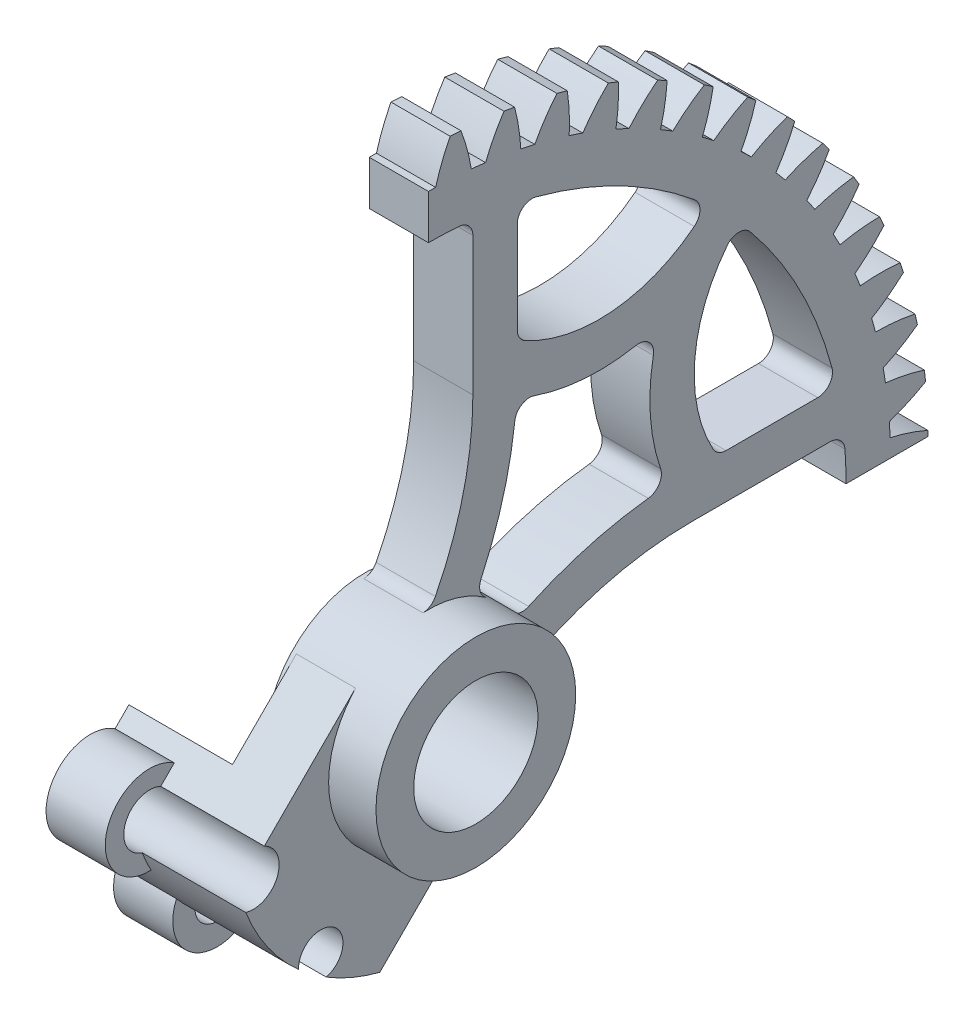
SolidWorks part; units mm, degrees
ref_plane "Plane1" through (0, 0, 0) normal (0, 0, 1) x (1, 0, 0)
ref_plane "Plane2" through (0, 0, 0) normal (0, 1, 0) x (1, 0, 0)
ref_plane "Plane3" through (0, 0, 0) normal (1, 0, 0) x (0, 0, -1)
sketch "HoldingSke" plane through (0, 0, 0) normal (0, 1, 0) x (1, 0, 0)
  line L0 (0, 0) -> (0.471, -0.7538)
  line L1 (-15, 0) -> (100, 0) construction
  line L2 (0, 0) -> (-2.1039, 2.3779)
  line L3 (0, 0) -> (-11.863, 4.5341)
  line L4 (0, 0) -> (4.5764, 7.3237)
  line L5 (0, 0) -> (-46.8476, -17.4728)
  line L6 (0, 0) -> (-3.3159, -2.2372)
  line L7 (-2.1039, 2.3779) -> (8.6586, 51.2059)
  line L8 (-76.2, 54.61) -> (-74.8, 54.61)
  line L9 (-71.009, 38.7566) -> (-53.1078, 45.2721)
  line L10 (-76.2, 71.12) -> (104.1128, 71.12)
  line L11 (0, 0) -> (-4, 0)
  line L12 (-76.2, 101.6) -> (-76.158, 101.6)
  line L13 (24.9733, 27.94) -> (52.9518, 28.4284)
  line L14 (24.9733, 27.94) -> (24.9743, 27.94)
  line L15 (24.9733, 27.94) -> (100.4006, 29.5858)
  line L16 (-63.627, -1.125) -> (-12.827, -1.125)
  circle A0 centre (0, 0) radius 4
  circle A1 centre (0, 0) radius 31.2177
  circle A2 centre (0, 0) radius 37.5
  circle A3 centre (0, 0) radius 4
  dimension "MHD" = 62.4355
  dimension "Hub_dia" = 75
  dimension "Bore" = 8
  dimension "MBD" = 8
  dimension "Num_teeth" = 58
  dimension "Pitch" = 0.8889
  dimension "Overall_len" = 50
  dimension "Show_teeth" = 58
  dimension "Thickness" = 4
  dimension "OAL" = 50.0001
  dimension "T_dim" = 1.4
  dimension "Ap" = 20
  dimension "H" = 19.05
  dimension "Pitch_radius" = 180.3128
  dimension "Width" = 4
  dimension "Backlash" = 0.042
  dimension "Addendum_fac" = 1
  dimension "Dedendum_fac" = 1.25
  dimension "Clearance_fac" = 0.25
  dimension "Dedendum_add" = 0.001
  dimension "Module" = 1.125
sketch "BasProSke" plane through (0, 0, 0) normal (0, 1, 0) x (1, 0, 0)
  line L0 (-10, 0) -> (60, 0) construction
  line L1 (0, 0) -> (0, 33.75)
  line L2 (0, 0) -> (4, 0)
  line L3 (4, 0) -> (4, 33.75)
  line L4 (4, 33.75) -> (0, 33.75)
  dimension "Thickness" = 4
  dimension "Diameter" = 67.5
revolve "Base-Revolve" add sketch "BasProSke" angle 360 about L0
sketch "TooCutSke" plane through (0, 0, 0) normal (1, 0, 0) x (0, 0, -1)
  line L1 (0, 0) -> (0, 107) construction
  line L2 (0, 0) -> (-0.957, 32.611) construction
  line L3 (0, 0) -> (-3.5315, 65.1342) construction
  line L4 (-0.957, 32.611) -> (-1.7657, 32.5671) construction
  arc A0 (0.4842, 31.214) -> (-0.4842, 31.214) centre (0, 0) ccw
  arc A1 (1.477, 33.7431) -> (-1.477, 33.7431) centre (0, 0) ccw
  circle A2 centre (0, 0) radius 32.625 construction
  circle A3 centre (0, 0) radius 30.6575 construction
  arc A4 (-0.4842, 31.214) -> (-1.477, 33.7431) centre (-13.0621, 27.7356) ccw
  arc A5 (1.477, 33.7431) -> (0.4842, 31.214) centre (13.0621, 27.7356) ccw
  dimension "Root_dia" = 62.4355
  dimension "Overcut_dia" = 67.5508
  dimension "Pitch_dia" = 65.25
  dimension "Base_dia" = 61.3149
  dimension "Flank_rad" = 13.05
  dimension "Half_ang" = 3.103
  dimension "Half_CT" = 0.81
extrude "ToothCut" cut sketch "TooCutSke" along normal through all
fillet "Breaks" [suppressed] radius 0.0225 tangent propagation no
fillet "RootFillets" [suppressed] radius 0.2823
pattern_circular "TeethCuts" count 58 every 6.207 about axis through (-10, 0, 0) along (1, 0, 0) of "ToothCut", "RootFillets", "Breaks"
sketch "HubNeaOneSke" plane through (0, 0, 0) normal (-1, 0, 0) x (0, 0, 1)
  circle A0 centre (0, 0) radius 31.2177
  dimension "Diameter" = 62.4355
extrude "HubNearOne" [suppressed] add sketch "HubNeaOneSke" along normal blind 46.0001
sketch "HubNeaBotSke" plane through (0, 0, 0) normal (-1, 0, 0) x (0, 0, 1)
  circle A0 centre (0, 0) radius 31.2177
  dimension "Diameter" = 62.4355
extrude "HubNearBoth" [suppressed] add sketch "HubNeaBotSke" along normal blind 23
ref_plane "FarPln" through (4, 0, 0) normal (1, 0, 0) x (0, 0, -1)
sketch "HubFarSke" plane through (4, 0, 0) normal (1, 0, 0) x (0, 0, -1)
  circle A0 centre (0, 0) radius 31.2177
  dimension "Diameter" = 62.4355
extrude "HubFar" [suppressed] add sketch "HubFarSke" along normal blind 23
sketch "BorSke" plane through (0, 0, 0) normal (1, 0, 0) x (0, 0, -1)
  circle A0 centre (0, 0) radius 4.25
  dimension "Diameter" = 8.5
extrude "Bore" cut sketch "BorSke" along normal mid plane 100.0001
sketch "KeySke" plane through (0, 0, 0) normal (1, 0, 0) x (0, 0, -1)
  line L0 (-1.5, 0) -> (-1.5, 5.4)
  line L1 (-1.5, 5.4) -> (1.5, 5.4)
  line L2 (1.5, 5.4) -> (1.5, 0)
  line L3 (0, 0) -> (0, 34) construction
  line L4 (-1.5, 0) -> (1.5, 0)
  dimension "Offset" = 5.4
  dimension "Width" = 3
extrude "Keyway" [suppressed] cut sketch "KeySke" along normal mid plane 100.0001
pattern_circular "Keyway2" [suppressed] count 2 every 90 about axis through (-10, 0, 0) along (1, 0, 0) reverse direction yes
sketch "cutoff" plane through (0, 0, 0) normal (1, 0, 0) x (0, 0, -1)
  line L0 (17.8096, 0) -> (35.6193, 0)
  line L1 (0, 17.8096) -> (0, 35.6193)
  line L2 (0, 35.6193) -> (0, 0) construction
  arc A0 (-5.0543, 4.4739) -> (4.4739, -5.0543) centre (0, 0) ccw
  circle A1 centre (0, 0) radius 4.25 construction
  arc A2 (0, 35.6193) -> (35.6193, 0) centre (0, 0) ccw
  arc A3 (0, 17.8096) -> (-5.0543, 4.4739) centre (-20.1201, 17.8096) cw
  arc A4 (17.8096, 0) -> (4.4739, -5.0543) centre (17.8096, -20.1201) ccw
  dimension "D1" = 2.5
extrude "Cut-Extrude1" cut sketch "cutoff" along normal up to next
sketch "Sketch3" plane through (4, 0, 0) normal (1, 0, 0) x (0, 0, -1)
  circle A0 centre (0, 0) radius 6.75
  arc A1 (-5.0543, 4.4739) -> (4.4739, -5.0543) centre (0, 0) ccw construction
  arc A2 (-5.0543, 4.4739) -> (4.4739, -5.0543) centre (0, 0) ccw construction
extrude "Boss-Extrude1" add sketch "Sketch3" along normal blind 3.2
sketch "Sketch4" plane through (4, 0, 0) normal (1, 0, 0) x (0, 0, -1)
  line L0 (0, 0) -> (-9.3692, -9.3692) construction
  line L1 (17.8096, 0) -> (33.75, 0) construction
  line L2 (-4.773, 4.773) -> (-12.8352, -3.2893)
  line L3 (4.773, -4.773) -> (-3.2893, -12.8352)
  circle A0 centre (0, 0) radius 6.75 construction
  arc A1 (4.773, -4.773) -> (-4.773, 4.773) centre (0, 0) ccw
  arc A4 (-9.2451, 0.3008) -> (0.3008, -9.2451) centre (0, 0) ccw construction
  arc A7 (-12.8352, -3.2893) -> (-3.2893, -12.8352) centre (0, 0) ccw
  circle A10 centre (0, 0) radius 13.25 construction
  circle A11 centre (0, 0) radius 9.25 construction
  circle A12 centre (0, 0) radius 6.75 construction
  dimension "D3" = 4
  dimension "D1" = 135
  dimension "D2" = 2.5
extrude "Boss-Extrude2" add sketch "Sketch4" against normal up to surface (4 mm away) up to face at (0, 0, -4.25)
sketch "Sketch5" plane through (0, 0, 0) normal (-1, 0, 0) x (0, 0, 1)
  line L2 (12.8352, -3.2893) -> (4.773, 4.773)
  line L3 (-4.773, -4.773) -> (3.2893, -12.8352)
  line L4 (12.8352, -3.2893) -> (9.2451, 0.3008)
  line L5 (-0.3008, -9.2451) -> (3.2893, -12.8352)
  arc A0 (-0.3008, -9.2451) -> (9.2451, 0.3008) centre (0, 0) ccw construction
  arc A1 (-0.3008, -9.2451) -> (9.2451, 0.3008) centre (0, 0) ccw
  arc A2 (3.2893, -12.8352) -> (12.8352, -3.2893) centre (0, 0) ccw
  arc A3 (4.773, 4.773) -> (-4.773, -4.773) centre (0, 0) ccw
  arc A4 (3.2893, -12.8352) -> (12.8352, -3.2893) centre (0, 0) ccw
  dimension "D1" = 0
extrude "Boss-Extrude3" add sketch "Sketch5" along normal blind 7
sketch "Sketch11" plane through (-7, 0, 0) normal (-1, 0, 0) x (0, 0, 1)
  line L5 (0, 0) -> (16, 0) construction
  line L6 (16, 0) -> (16, -2) construction
  line L7 (16, -2) -> (10.2905, -11.6366) construction
  line L8 (0, 0) -> (0, -2) construction
  line L9 (0, -2) -> (4.0758, -11.2623) construction
  arc A1 (4.0758, -11.2623) -> (10.2905, -11.6366) centre (7.2794, -9.8526) ccw construction
  circle A2 centre (7.2794, -9.8526) radius 1.5 construction
  circle A3 centre (7.2794, -9.8526) radius 3
  circle A4 centre (11.8433, -3.1303) radius 1.5 construction
  circle A5 centre (11.8433, -3.1303) radius 3
extrude "Boss-Extrude4" add sketch "Sketch11" against normal blind 4
sketch "Sketch12" plane through (-7, 0, 0) normal (-1, 0, 0) x (0, 0, 1)
  circle A5 centre (7.2794, -9.8526) radius 1.5 construction
  circle A6 centre (7.2794, -9.8526) radius 1.5
  circle A9 centre (11.8433, -3.1303) radius 1.75
  circle A15 centre (11.8433, -3.1303) radius 1.75
  dimension "D1" = 0.25
extrude "Cut-Extrude2" cut sketch "Sketch12" against normal through all
sketch "Sketch14" plane through (0, 0, 0) normal (-1, 0, 0) x (0, 0, 1)
  circle A0 centre (0, 0) radius 6.75
  circle A1 centre (0, 0) radius 6.75 construction
extrude "Boss-Extrude5" add sketch "Sketch14" along normal blind 0.3
sketch "Sketch15" plane through (7.2, 0, 0) normal (1, 0, 0) x (0, 0, -1)
  circle A0 centre (0, 0) radius 4.2
  dimension "D1" = 8.4
extrude "Cut-Extrude3" cut sketch "Sketch15" against normal through all
sketch "Sketch18" plane through (4, 0, 0) normal (1, 0, 0) x (0, 0, -1)
  line L0 (19.953, 19.953) -> (731.1102, 731.1102) construction
  line L1 (28.2178, 0) -> (17.8096, 0)
  line L2 (3, 31.0733) -> (3, 17.8096) construction
  line L3 (6, 27.5725) -> (6, 19.5357)
  line L4 (3, 31.2178) -> (3, 17.8096)
  line L5 (3, 28.0578) -> (3, 17.8096)
  line L7 (6, 31.0733) -> (6, 17.8096) construction
  line L8 (28.0578, 3) -> (17.8096, 3)
  line L9 (0, 31.2178) -> (0, 17.8096) construction
  line L11 (0, 28.2177) -> (0, 17.8096)
  line L12 (27.5725, 6) -> (19.5357, 6)
  line L14 (0, 0) -> (15.5914, 15.5914) construction
  arc A0 (6, 17.8096) -> (19.953, 19.953) centre (11.5158, 28.3901) ccw construction
  arc A1 (6, 19.5357) -> (18.864, 20.9855) centre (11.5158, 28.3901) ccw
  arc A2 (5.9483, 16.1664) -> (15.5914, 15.5914) centre (11.5158, 28.3901) ccw
  arc A3 (19.5357, 6) -> (20.9855, 18.864) centre (28.3901, 11.5158) cw
  arc A4 (16.1664, 5.9483) -> (15.5914, 15.5914) centre (28.3901, 11.5158) cw
  arc A5 (-2.6636, 2.6502) -> (3, 17.8096) centre (-20.1201, 17.8096) ccw
  arc A6 (0.1818, 6.7476) -> (3, 17.8096) centre (-20.1201, 17.8096) ccw
  arc A8 (5.9647, 3.1599) -> (16.1664, 5.9483) centre (17.8096, -20.1201) cw
  arc A9 (4.4739, -5.0543) -> (6.7476, 0.1818) centre (0, 0) ccw
  arc A10 (4.4739, -5.0543) -> (17.8096, 0) centre (17.8096, -20.1201) cw
  arc A11 (28.0578, 3) -> (28.2178, 0) centre (0, 0) cw
  arc A12 (-5.0543, 4.4739) -> (0, 17.8096) centre (-20.1201, 17.8096) ccw
  arc A16 (3.1599, 5.9647) -> (5.9483, 16.1664) centre (-20.1201, 17.8096) ccw
  arc A17 (3, 28.0578) -> (0, 28.2177) centre (0, 0) ccw
  arc A19 (6.7476, 0.1818) -> (17.8096, 3) centre (17.8096, -20.1201) cw
  arc A20 (-2.6636, 2.6502) -> (3, 17.8096) centre (-20.1201, 17.8096) ccw construction
  arc A21 (-0.3985, 0.6831) -> (6, 17.8096) centre (-20.1201, 17.8096) ccw construction
  arc A22 (27.5725, 6) -> (20.9855, 18.864) centre (0, 0) ccw
  arc A23 (18.864, 20.9855) -> (6, 27.5725) centre (0, 0) ccw
  circle A25 centre (0, 0) radius 6.75 construction
  arc A26 (5.9647, 3.1599) -> (3.1599, 5.9647) centre (0, 0) ccw
  arc A27 (-5.0543, 4.4739) -> (0.1818, 6.7476) centre (0, 0) cw
  arc A28 (4.773, -4.773) -> (-4.773, 4.773) centre (0, 0) ccw construction
  arc A29 (-4.9287, 4.6172) -> (0, 17.8096) centre (-20.1201, 17.8096) ccw construction
  dimension "D2" = 3
  dimension "D5" = 1.5
  dimension "D1" = 3
  dimension "D4" = 3
extrude "Cut-Extrude4" cut sketch "Sketch18" against normal up to next
fillet "Fillet1" radius 1 15 edges at (2, 15.5914, -15.5914) (2, 6.7476, -0.1818) (2, 28.0578, -3) (2, 3, -28.0578) (2, 0.1818, -6.7476) (2, 20.9855, -18.864) (2, 18.864, -20.9855) (2, 6, -19.5357) (2, 6, -27.5725) (2, 5.9483, -16.1664) (2, 3.1599, -5.9647) (2, 19.5357, -6) (2, 5.9647, -3.1599) (2, 27.5725, -6) (2, 16.1664, -5.9483)
equation "' \"Module@HoldingSke\" = 6.35"
equation "' \"Num_teeth@HoldingSke\" = 12"
equation "' \"Ap@HoldingSke\" =  20"
equation "' \"Ap@HoldingSke\" = 20"
equation "' \"Width@HoldingSke\" = 0.5 * 25.4"
equation "' \"Hub_dia@HoldingSke\"= 1 * 25.4"
equation "' \"Hub_dia@HoldingSke\" = 1 * 25.4"
equation "' \"Overall_len@HoldingSke\" = 1.0 * 25.4"
equation "' \"Bore@HoldingSke\" = 0.75 * 25.4"
equation "' \"T_dim@HoldingSke\" = 0.1 * 25.4"
equation "' \"Width@KeySke\" = 0.25 * 25.4"
equation "' \"Show_teeth@HoldingSke\" = 13"
equation "' \"Backlash@HoldingSke\" = 0.009 * 25.4"
equation "' \"Addendum_fac@HoldingSke\" = 1.0"
equation "' \"Dedendum_fac@HoldingSke\" = 1.25"
equation "' \"Dedendum_add@HoldingSke\" = 0.00005 * 25.4"
equation "' \"Clearance_fac@HoldingSke\" = 0.25"
equation "\"Pitch@HoldingSke\" = 1 / \"Module@HoldingSke\""
equation "\"Overcut_dia@TooCutSke\" = (\"Num_teeth@HoldingSke\" + 2 * \"Addendum_fac@HoldingSke\") / \"Pitch@HoldingSke\" + 0.002 * 25.4"
equation "\"Pitch_dia@TooCutSke\" = \"Num_teeth@HoldingSke\" / \"Pitch@HoldingSke\""
equation "\"Base_dia@TooCutSke\" = \"Num_teeth@HoldingSke\" / \"Pitch@HoldingSke\" * cos((\"Ap@HoldingSke\"  * 3.14159265 / 180))"
equation "\"Root_dia@TooCutSke\" = (\"Num_teeth@HoldingSke\" + 2) / \"Pitch@HoldingSke\" - 2 * (\"Addendum_fac@HoldingSke\" + \"Dedendum_fac@HoldingSke\") / \"Pitch@HoldingSke\" - \"Dedendum_add@HoldingSke\" * 2"
equation "\"Half_ang@TooCutSke\" = 180 / \"Num_teeth@HoldingSke\""
equation "\"Half_CT@TooCutSke\" = \"Num_teeth@HoldingSke\" / \"Pitch@HoldingSke\" * sin((3.14159265 / 2 / \"Num_teeth@HoldingSke\")) / 2 - 7 * \"Backlash@HoldingSke\" / 4"
equation "\"Flank_rad@TooCutSke\" = \"Num_teeth@HoldingSke\" / \"Pitch@HoldingSke\" / 5"
equation "\"Radius@RootFillets\" = \"Clearance_fac@HoldingSke\" / \"Pitch@HoldingSke\" + \"Dedendum_add@HoldingSke\""
equation "\"Break_rad@Breaks\" = 0.02 / \"Pitch@HoldingSke\""
equation "\"Thickness@HoldingSke\" = \"Width@HoldingSke\""
equation "\"OAL@HoldingSke\" = \"Thickness@HoldingSke\""
equation "\"MHD@HoldingSke\" = (\"Num_teeth@HoldingSke\" + 2) / \"Pitch@HoldingSke\" - 2 * (\"Addendum_fac@HoldingSke\" + \"Dedendum_fac@HoldingSke\")  / \"Pitch@HoldingSke\" - \"Dedendum_add@HoldingSke\" * 2"
equation "\"MBD@HoldingSke\" = (\"Num_teeth@HoldingSke\" + 2) / \"Pitch@HoldingSke\" - 2 * (\"Addendum_fac@HoldingSke\" + \"Dedendum_fac@HoldingSke\")  / \"Pitch@HoldingSke\" - \"Dedendum_add@HoldingSke\" * 2 - 0.002 * 25.4"
equation "\"MHD@HoldingSke\" = ((sgn( \"MHD@HoldingSke\" - \"Hub_dia@HoldingSke\" )-1)*( \"MHD@HoldingSke\" - \"Hub_dia@HoldingSke\" ))/-2+ \"Hub_dia@HoldingSke\""
equation "\"MBD@HoldingSke\" = ((sgn( \"MBD@HoldingSke\" - \"Bore@HoldingSke\" )-1)*( \"MBD@HoldingSke\" - \"Bore@HoldingSke\" ))/-2+ \"Bore@HoldingSke\""
equation "\"OAL@HoldingSke\" = ((sgn( \"OAL@HoldingSke\" - \"Overall_len@HoldingSke\" )+1)*( \"OAL@HoldingSke\" - \"Overall_len@HoldingSke\" ))/2 + \"Overall_len@HoldingSke\" + 0.000002 * 25.4"
equation "\"Num_teeth@TeethCuts\" = int( \"Show_teeth@HoldingSke\" ) + 1"
equation "\"Num_teeth@TeethCuts\" = ((sgn( \"Num_teeth@TeethCuts\" - \"Num_teeth@HoldingSke\" )-1)*( \"Num_teeth@TeethCuts\" - \"Num_teeth@HoldingSke\" ))/-2+ \"Num_teeth@HoldingSke\""
equation "\"Num_teeth@TeethCuts\" = ((sgn( \"Num_teeth@TeethCuts\" - 2.0)+1)*( \"Num_teeth@TeethCuts\" - 2.0))/2 +2.0"
equation "\"Angle@TeethCuts\" = 360.0 / \"Num_teeth@HoldingSke\""
equation "\"Diameter@BasProSke\" = (\"Num_teeth@HoldingSke\" + 2 * \"Addendum_fac@HoldingSke\") / \"Pitch@HoldingSke\""
equation "\"Thickness@BasProSke\"  = \"Thickness@HoldingSke\""
equation "' \"Fillet_rad@BasProSke\" =  \"Thickness@HoldingSke\" * 0.05"
equation "' \"Fillet_rad@BasProSke\" = \"Thickness@HoldingSke\" * 0.05"
equation "\"MHD@HoldingSke\" = ((sgn( \"MHD@HoldingSke\" - \"Root_dia@TooCutSke\" )-1)*( \"MHD@HoldingSke\" - \"Root_dia@TooCutSke\" ))/-2+ \"Root_dia@TooCutSke\""
equation "\"Diameter@HubNeaOneSke\" = \"MHD@HoldingSke\""
equation "\"Length@HubNearOne\" = \"OAL@HoldingSke\" - \"Thickness@BasProSke\""
equation "\"Diameter@HubNeaBotSke\" = \"MHD@HoldingSke\""
equation "\"Length@HubNearBoth\" = ( \"OAL@HoldingSke\" - \"Thickness@BasProSke\" ) / 2.0"
equation "\"Thickness@FarPln\" = \"Thickness@BasProSke\""
equation "\"Diameter@HubFarSke\" = \"MHD@HoldingSke\""
equation "\"Length@HubFar\" = ( \"OAL@HoldingSke\" - \"Thickness@BasProSke\" ) / 2.0"
equation "\"D1@Bore\" = \"OAL@HoldingSke\" * 2.0"
equation "\"D1@Keyway\" = \"OAL@HoldingSke\" * 2.0"
equation "\"Offset@KeySke\" = \"T_dim@HoldingSke\" + \"MBD@HoldingSke\" / 2.0"
equation "\"D5@Sketch18\"=\"D2@Sketch18\"/2"
